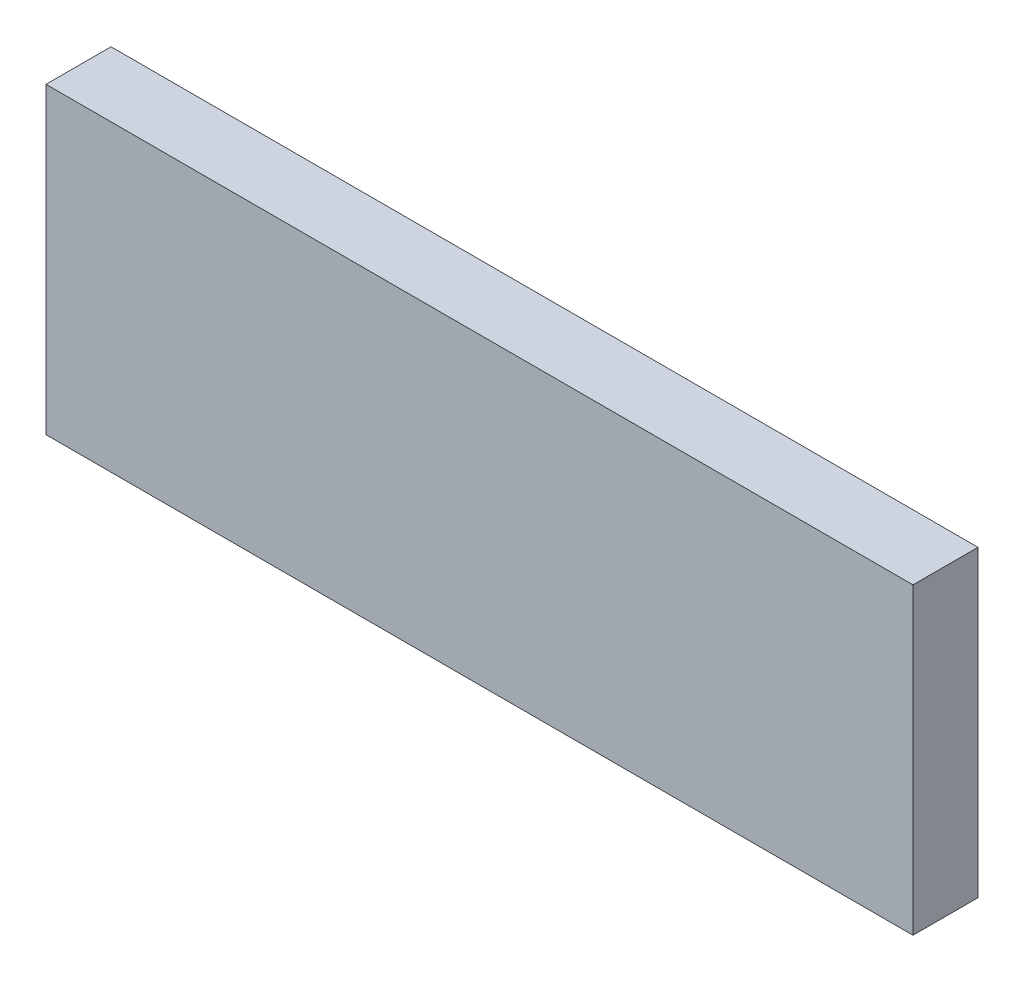
SolidWorks part; units mm, degrees
ref_plane "Alzado" through (0, 0, 0) normal (0, 0, 1) x (1, 0, 0)
ref_plane "Planta" through (0, 0, 0) normal (0, 1, 0) x (1, 0, 0)
ref_plane "Vista lateral" through (0, 0, 0) normal (1, 0, 0) x (0, 0, -1)
sketch "Croquis1" plane through (0, 0, 0) normal (0, 0, 1) x (1, 0, 0)
  line L1 (0, 0) -> (80, 0)
  line L2 (0, 0) -> (0, 28)
  line L3 (0, 28) -> (80, 28)
  line L4 (80, 0) -> (80, 28)
  dimension "D1" = 80
  dimension "D2" = 28
extrude "Saliente-Extruir1" add sketch "Croquis1" along normal blind 6
